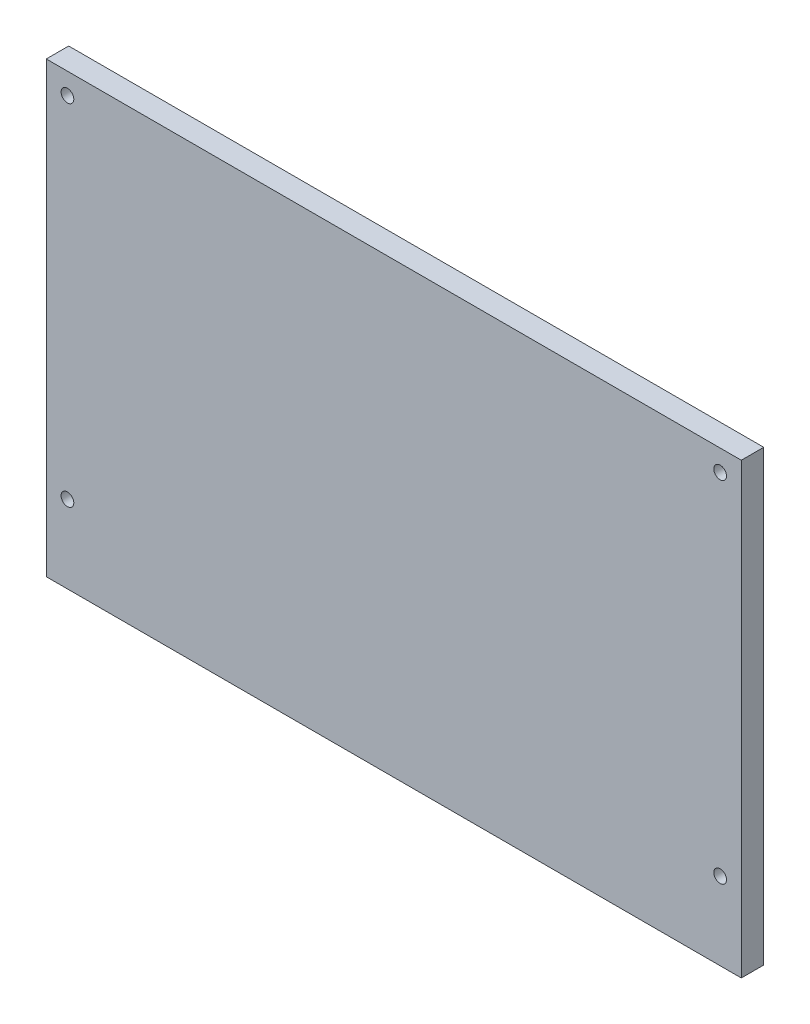
SolidWorks part; units mm, degrees
material "Acrylic (Medium-high impact)"
ref_plane "Front Plane" through (0, 0, 0) normal (0, 0, 1) x (1, 0, 0)
ref_plane "Top Plane" through (0, 0, 0) normal (0, 1, 0) x (1, 0, 0)
ref_plane "Right Plane" through (0, 0, 0) normal (1, 0, 0) x (0, 0, -1)
sketch "Sketch1" plane through (0, 0, 0) normal (0, 0, 1) x (1, 0, 0)
  line L1 (196.85, 127) -> (0, 127)
  line L2 (196.85, 127) -> (196.85, 0)
  line L3 (196.85, 0) -> (0, 0)
  line L4 (0, 127) -> (0, 0)
  line L5 (196.85, 127) -> (0, 0) construction
  line L6 (196.85, 0) -> (0, 127) construction
  point P0 (98.425, 63.5)
  dimension "D1" = 127
  dimension "D2" = 196.85
extrude "Boss-Extrude1" add sketch "Sketch1" along normal blind 6.35
hole_wizard "M3 Clearance Hole1" positions "Sketch2" profile "Sketch3" hole size "M3" standard "ANSI Metric" end condition through all
sketch "Sketch2" plane through (0, 0, 6.35) normal (0, 0, 1) x (1, 0, 0)
  line L0 (0, 127) -> (0, 0) construction
  line L1 (196.85, 127) -> (0, 127) construction
  line L2 (196.85, 0) -> (196.85, 127) construction
  line L3 (0, 0) -> (196.85, 0) construction
  point P0 (5.9944, 121.0056)
  point P2 (5.9944, 21.9964)
  point P4 (190.8556, 21.9964)
  point P6 (190.8556, 121.0056)
  dimension "D1" = 5.9944
  dimension "D2" = 5.9944
  dimension "D3" = 5.9944
  dimension "D4" = 21.9964
sketch "Sketch3" plane through (5.9944, 121.0056, 6.35) normal (1, 0, 0) x (0, -1, 0)
  line L0 (0, 0) -> (0, 6.35)
  line L1 (0, 6.35) -> (1.8, 6.35)
  line L2 (1.8, 6.35) -> (1.8, 0)
  line L5 (1.8, 0) -> (0, 0)
  line L11 (0, -6.35) -> (0, 107.95) construction
  dimension "Thru Hole Dia." = 3.6
  dimension "Thru Hole Depth" = 6.35
sketch "Sketch4" plane through (0, 0, 6.35) normal (0, 0, 1) x (1, 0, 0)
  line L0 (0, 127) -> (0, 0) construction
  line L1 (46.99, 107.95) -> (50.4952, 107.95)
  line L2 (46.99, 107.95) -> (46.99, 44.45)
  line L3 (46.99, 44.45) -> (50.4952, 44.45)
  line L4 (50.4952, 107.95) -> (50.4952, 44.45)
  line L5 (146.3548, 107.95) -> (149.86, 107.95)
  line L6 (146.3548, 107.95) -> (146.3548, 44.45)
  line L7 (146.3548, 44.45) -> (149.86, 44.45)
  line L8 (149.86, 107.95) -> (149.86, 44.45)
  line L9 (196.85, 0) -> (196.85, 127) construction
  line L10 (196.85, 127) -> (0, 127) construction
  dimension "D1" = 3.5052
  dimension "D2" = 63.5
  dimension "D3" = 46.99
  dimension "D4" = 46.99
  dimension "D5" = 19.05
extrude "Cut-Extrude1" [suppressed] cut sketch "Sketch4" against normal through all
sketch "Sketch5" plane through (0, 0, 6.35) normal (0, 0, 1) x (1, 0, 0)
  line L0 (0, 10.7092) -> (76.2, 0)
  line L1 (0, 127) -> (0, 0) construction
  line L2 (0, 0) -> (196.85, 0) construction
  line L3 (76.2, 0) -> (0, 0)
  line L4 (0, 0) -> (0, 10.7092)
  line L5 (120.65, 0) -> (196.85, 0)
  line L6 (196.85, 0) -> (196.85, 10.7092)
  line L7 (196.85, 0) -> (196.85, 127) construction
  line L8 (196.85, 10.7092) -> (120.65, 0)
  dimension "D1" = 8
  dimension "D2" = 8
  dimension "D3" = 76.2
  dimension "D4" = 76.2
extrude "Cut-Extrude2" [suppressed] cut sketch "Sketch5" against normal through all
